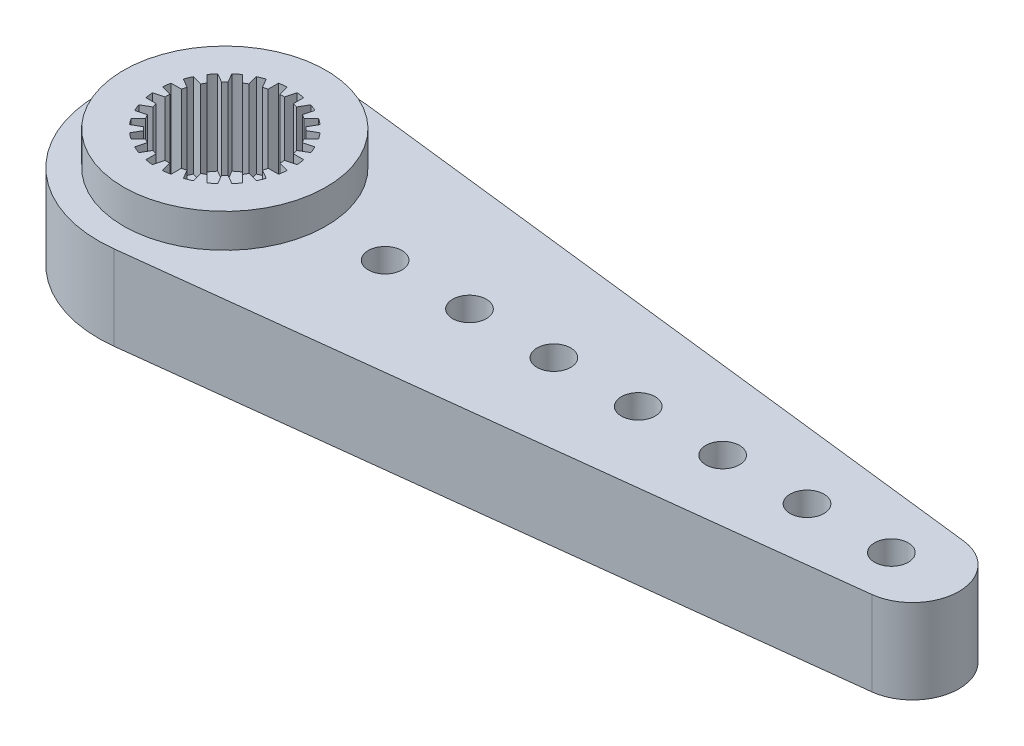
SolidWorks part; units mm, degrees
ref_plane "Plan de face" through (0, 0, 0) normal (0, 0, 1) x (1, 0, 0)
ref_plane "Plan de dessus" through (0, 0, 0) normal (0, 1, 0) x (1, 0, 0)
ref_plane "Plan de droite" through (0, 0, 0) normal (1, 0, 0) x (0, 0, -1)
sketch "Esquisse1" plane through (0, 0, 0) normal (0, 1, 0) x (1, 0, 0)
  line L0 (0.8742, -7.4489) -> (41.0706, -2.7313)
  line L1 (41.0706, 2.7313) -> (0.8742, 7.4489)
  line L2 (-7.5, 27.3999) -> (-7.5, -15.4168) construction
  line L3 (-7.5, -15.4168) -> (43.5, -15.4168) construction
  line L4 (43.5, -15.4168) -> (43.5, 24.8813) construction
  arc A0 (0.8742, 7.4489) -> (0.8742, -7.4489) centre (0, 0) ccw
  arc A1 (41.0706, -2.7313) -> (41.0706, 2.7313) centre (40.75, 0) ccw
  circle A2 centre (0, 0) radius 1.6
  dimension "D1" = 2.75
  dimension "D2" = 7.5
  dimension "D4" = 3.2
  dimension "D3" = 51
extrude "Boss.-Extru.1" add sketch "Esquisse1" along normal blind 8
sketch "Esquisse2" plane through (0, 8, 0) normal (0, 1, 0) x (1, 0, 0)
  line L0 (0, 0) -> (46.1588, 0) construction
  line L1 (-7.5, 15.192) -> (-7.5, -12.3349) construction
  circle A0 centre (9.5, 0) radius 1
  arc A1 (0.8742, 7.4489) -> (0.8742, -7.4489) centre (0, 0) ccw construction
  dimension "D1" = 2
  dimension "D2" = 17
extrude "Enlèv. mat.-Extru.1" cut sketch "Esquisse2" against normal blind 8
pattern_linear "Répétition linéaire1" count 7 spacing 5 along (1, 0, 0) of "Enlèv. mat.-Extru.1"
sketch "Esquisse3" plane through (0, 8, 0) normal (0, 1, 0) x (1, 0, 0)
  line L1 (-12.783, 10.2172) -> (50.2427, 10.2172)
  line L2 (-12.783, 10.2172) -> (-12.783, -12.2303)
  line L3 (-12.783, -12.2303) -> (50.2427, -12.2303)
  line L4 (50.2427, 10.2172) -> (50.2427, -12.2303)
  circle A0 centre (0, 0) radius 6
  dimension "D1" = 12
extrude "Enlèv. mat.-Extru.2" cut sketch "Esquisse3" against normal blind 2
sketch "Esquisse4" plane through (0, 0, 0) normal (0, -1, 0) x (1, 0, 0)
  line L1 (-13.4769, 12.3588) -> (51.6733, 12.3588)
  line L2 (-13.4769, 12.3588) -> (-13.4769, -11.2271)
  line L3 (-13.4769, -11.2271) -> (51.6733, -11.2271)
  line L4 (51.6733, 12.3588) -> (51.6733, -11.2271)
  circle A0 centre (0, 0) radius 4.65
  dimension "D1" = 9.3
extrude "Enlèv. mat.-Extru.3" cut sketch "Esquisse4" against normal blind 1
sketch "Esquisse5" plane through (0, 0, 0) normal (0, -1, 0) x (1, 0, 0)
  circle A0 centre (0, 0) radius 2.75
  dimension "D1" = 5.5
extrude "Enlèv. mat.-Extru.4" cut sketch "Esquisse5" against normal blind 1
chamfer "Chanfrein1" distance 1 angle 45 1 edges at (0, 1, -4.65)
sketch "Esquisse6" plane through (0, 8, 0) normal (0, 1, 0) x (1, 0, 0)
  circle A0 centre (0, 0) radius 4
  dimension "D1" = 8
extrude "Enlèv. mat.-Extru.5" cut sketch "Esquisse6" against normal blind 5
sketch "Esquisse7" plane through (0, 8, 0) normal (0, 1, 0) x (1, 0, 0)
  line L0 (0, 0) -> (0, -6.8034) construction
  line L1 (0, -6.8034) -> (2.7804, -4) construction
  line L2 (2.7804, -4) -> (-2.8896, -4) construction
  line L3 (0.3, -4) -> (0.1392, -3.4)
  line L4 (0.1392, -3.4) -> (-0.1392, -3.4)
  line L5 (-0.1392, -3.4) -> (-0.3, -4)
  line L6 (-0.3, -4) -> (0.3, -4)
  circle A0 centre (0, 0) radius 4 construction
  point P9 (0.2492, -4.5)
  point P12 (0.1326, -3.9)
  point P13 (1.0385, -5.474)
  point P14 (-0.1634, -3.9)
  dimension "D1" = 0.6
  dimension "D2" = 0.6
  dimension "D3" = 15
extrude "Boss.-Extru.2" add sketch "Esquisse7" against normal up to surface (5 mm away) up to face at (0, 3, 1.6)
pattern_circular "Répétition circulaire1" count 24 over 360 about axis through (0, 8, 0) along (0, -1, 0) of "Boss.-Extru.2"
